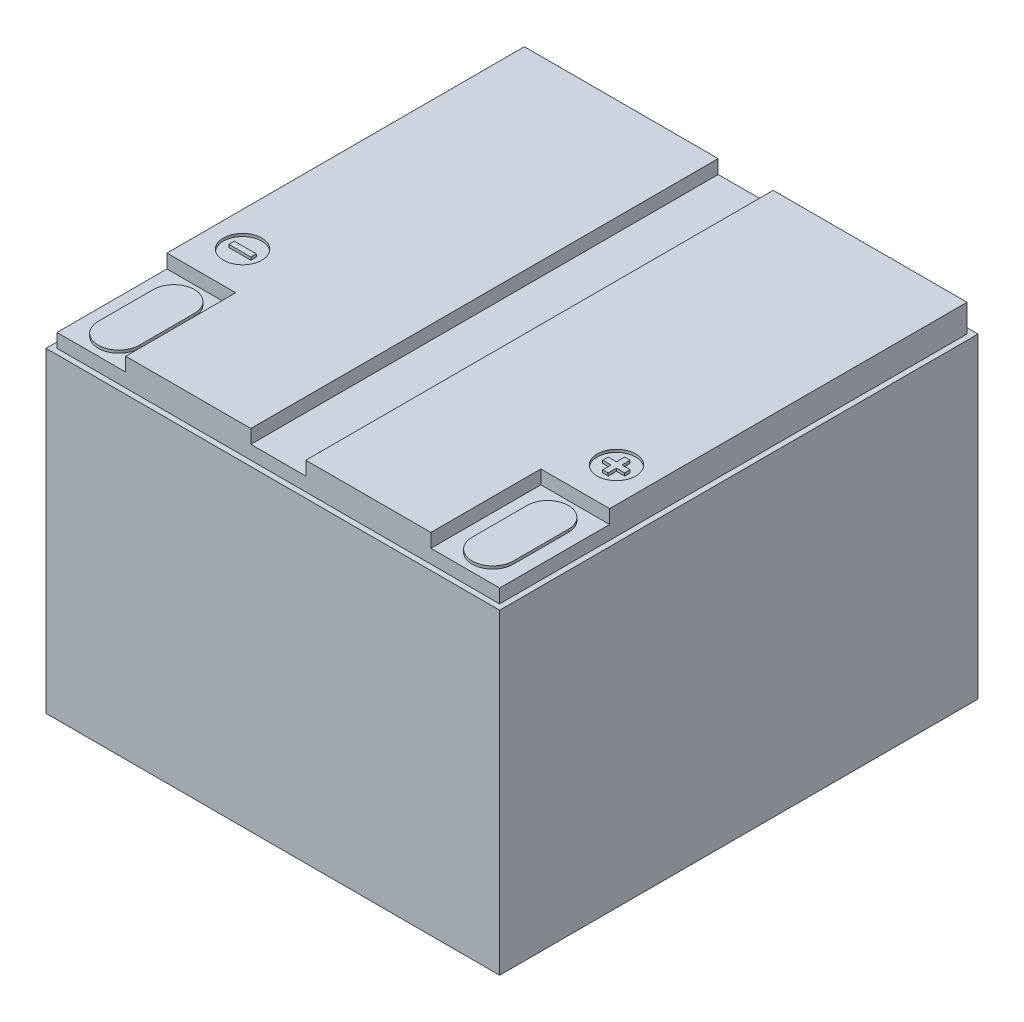
SolidWorks part; units mm, degrees
material "Polybutadiene (PB)"
ref_plane "Front Plane" through (0, 0, 0) normal (0, 0, 1) x (1, 0, 0)
ref_plane "Top Plane" through (0, 0, 0) normal (0, 1, 0) x (1, 0, 0)
ref_plane "Right Plane" through (0, 0, 0) normal (1, 0, 0) x (0, 0, -1)
sketch "Sketch1" plane through (0, 0, 0) normal (0, 1, 0) x (1, 0, 0)
  line L0 (-68, -85) -> (-68, 85) construction
  line L1 (80.5, 85) -> (-80.5, 85)
  line L2 (80.5, 85) -> (80.5, -85)
  line L3 (80.5, -85) -> (-80.5, -85)
  line L4 (-80.5, 85) -> (-80.5, -85)
  line L5 (80.5, 85) -> (-80.5, -85) construction
  line L6 (80.5, -85) -> (-80.5, 85) construction
  line L7 (-80.5, -85) -> (-55.5, -85)
  line L8 (-80.5, -85) -> (-80.5, -45)
  line L9 (-80.5, -45) -> (-55.5, -45)
  line L10 (-55.5, -85) -> (-55.5, -45)
  line L11 (-55.5, -65) -> (-68, -65) construction
  line L13 (-68, -55) -> (-68, -75) construction
  line L14 (-60.5, -55) -> (-60.5, -75)
  line L15 (-75.5, -55) -> (-75.5, -75)
  line L16 (0, 85) -> (0, -85) construction
  line L17 (68, -55) -> (68, -75) construction
  line L18 (60.5, -55) -> (60.5, -75)
  line L19 (75.5, -55) -> (75.5, -75)
  line L20 (80.5, -45) -> (55.5, -45)
  line L21 (55.5, -85) -> (55.5, -45)
  line L22 (80.5, -85) -> (55.5, -85)
  line L23 (80.5, -85) -> (80.5, -45)
  line L25 (-64, -29) -> (-72, -29)
  line L26 (-64, -29) -> (-64, -31)
  line L27 (-64, -31) -> (-72, -31)
  line L28 (-72, -29) -> (-72, -31)
  line L29 (-64, -29) -> (-72, -31) construction
  line L30 (-64, -31) -> (-72, -29) construction
  line L31 (72, -29) -> (64, -29)
  line L32 (72, -29) -> (72, -31)
  line L33 (72, -31) -> (64, -31)
  line L34 (64, -29) -> (64, -31)
  line L35 (72, -29) -> (64, -31) construction
  line L36 (72, -31) -> (64, -29) construction
  line L37 (69, -26) -> (67, -26)
  line L38 (69, -26) -> (69, -34)
  line L39 (69, -34) -> (67, -34)
  line L40 (67, -26) -> (67, -34)
  line L41 (69, -26) -> (67, -34) construction
  line L42 (69, -34) -> (67, -26) construction
  line L43 (-10, -85) -> (10, -85)
  line L44 (-10, -85) -> (-10, 85)
  line L45 (-10, 85) -> (10, 85)
  line L46 (10, -85) -> (10, 85)
  line L47 (82.5, 87) -> (-82.5, 87)
  line L48 (82.5, 87) -> (82.5, -87)
  line L49 (82.5, -87) -> (-82.5, -87)
  line L50 (-82.5, 87) -> (-82.5, -87)
  line L51 (82.5, 87) -> (-82.5, -87) construction
  line L52 (82.5, -87) -> (-82.5, 87) construction
  circle A0 centre (-68, -30) radius 7
  arc A1 (-60.5, -55) -> (-75.5, -55) centre (-68, -55) ccw
  arc A2 (-75.5, -75) -> (-60.5, -75) centre (-68, -75) ccw
  arc A3 (60.5, -55) -> (75.5, -55) centre (68, -55) cw
  arc A4 (75.5, -75) -> (60.5, -75) centre (68, -75) cw
  circle A5 centre (68, -30) radius 7
  point P0 (0, 0)
  point P12 (-68, -45)
  point P18 (-68, -65)
  point P27 (68, -65)
  point P53 (0, -85)
  point P54 (0, 0)
  dimension "D5" = 14
  dimension "D1" = 170
  dimension "D2" = 161
  dimension "D3" = 40
  dimension "D4" = 25
  dimension "D6" = 15
  dimension "D7" = 20
  dimension "D8" = 15
  dimension "D9" = 2
  dimension "D10" = 8
  dimension "D11" = 20
  dimension "D12" = 165
  dimension "D13" = 174
extrude "Boss-Extrude3" add sketch "Sketch1" along normal blind 125 contours L25 L28 L27 L26 | L46 L3 L21 L20 L2 L1 A5 | L3 L44 L1 L4 L9 L10 A0 | L38 L39 L40 L37 | L31 L34 L33 L32 region at (42.8262, 0, -6.4276) region at (-42.8262, 0, -6.4276) region at (-68, 0, 30)
extrude "Boss-Extrude4" add sketch "Sketch1<6>" along normal blind 124 contours A5 | A0
sketch "Sketch1<6>" plane through (0, 0, 0) normal (0, 1, 0) x (1, 0, 0) same geometry as "Sketch1"
extrude "Boss-Extrude5" add sketch "Sketch1<7>" along normal blind 120 contours L3 L10 L9 L4 A2 L15 A1 L14 | L21 L3 L2 L20 L19 A4 L18 A3 | L3 L46 L1 L44 | L44 L43 L46 L45 region at (0, 0, 0) region at (80.0283, 0, 65) region at (-68, 0, 45.4717)
sketch "Sketch1<7>" plane through (0, 0, 0) normal (0, 1, 0) x (1, 0, 0) same geometry as "Sketch1"
extrude "Boss-Extrude6" add sketch "Sketch1<8>" along normal blind 121 contours A4 L19 A3 L18 | L15 A2 L14 A1 region at (68, 0, 65)
sketch "Sketch1<8>" plane through (0, 0, 0) normal (0, 1, 0) x (1, 0, 0) same geometry as "Sketch1"
extrude "Boss-Extrude7" add sketch "Sketch1<10>" along normal blind 115 contours L48 L49 L50 L47
sketch "Sketch1<10>" plane through (0, 0, 0) normal (0, 1, 0) x (1, 0, 0) same geometry as "Sketch1"
